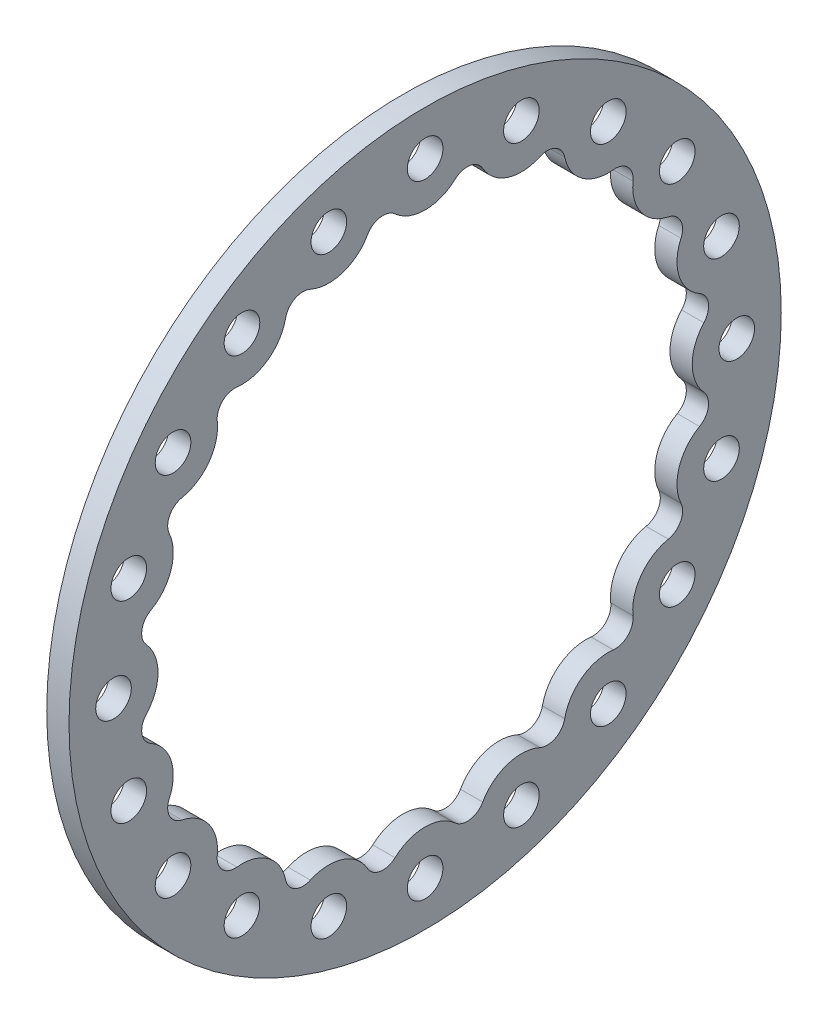
SolidWorks part; units mm, degrees
material "Delrin 2700 NC010, Low Viscosity Acetal Copolymer (SS)"
ref_plane "Front Plane" through (0, 0, 0) normal (0, 0, 1) x (1, 0, 0)
ref_plane "Top Plane" through (0, 0, 0) normal (0, 1, 0) x (1, 0, 0)
ref_plane "Right Plane" through (0, 0, 0) normal (1, 0, 0) x (0, 0, -1)
sketch "Sketch1" plane through (0, 0, 0) normal (1, 0, 0) x (0, 0, -1)
  circle A0 centre (0, 0) radius 80
  circle A1 centre (0, 0) radius 60
  dimension "D1" = 160
  dimension "D2" = 120
extrude "Boss-Extrude1" add sketch "Sketch1" along normal mid plane 5
sketch "Sketch2" plane through (2.5, 0, 0) normal (1, 0, 0) x (0, 0, -1)
  line L0 (0, 80) -> (0, 60) construction
  line L1 (-7.9969, 55.9452) -> (7.9969, 55.9452)
  line L2 (-9.451, 59.6715) -> (0, 0) construction
  line L3 (0, 0) -> (9.451, 59.6715) construction
  circle A0 centre (0, 70) radius 4
  circle A1 centre (0, 0) radius 80 construction
  arc A3 (-7.9969, 55.9452) -> (-6.7507, 62.6225) centre (-9.451, 59.6715) cw
  arc A4 (-6.7507, 62.6225) -> (6.7507, 62.6225) centre (0, 70) ccw
  arc A5 (7.9969, 55.9452) -> (6.7507, 62.6225) centre (9.451, 59.6715) ccw
  circle A6 centre (0, 0) radius 60 construction
  dimension "D1" = 8
  dimension "D2" = 18
extrude "Cut-Extrude1" cut sketch "Sketch2" against normal through all
pattern_circular "CirPattern1" count 20 over 360 about axis through (2.5, 0, 0) along (-1, 0, 0) of "Cut-Extrude1"
ref_axis "Axis1" through (2.5, 0, 0) along (-1, 0, 0)
